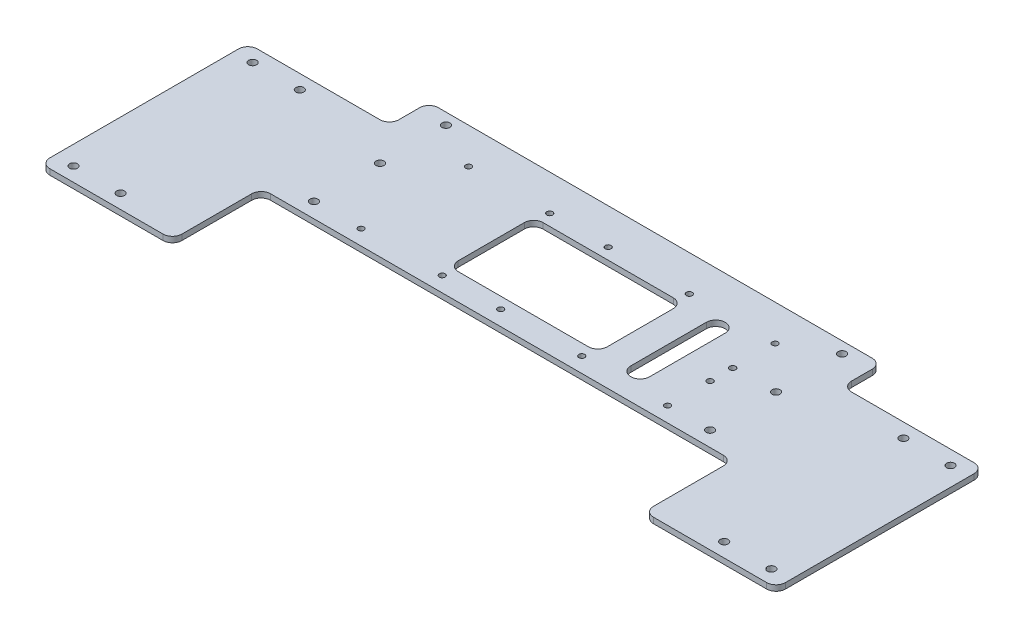
SolidWorks part; units mm, degrees
material "Thornel Mat VMA"
ref_plane "前视基准面" through (0, 0, 0) normal (0, 0, 1) x (1, 0, 0)
ref_plane "上视基准面" through (0, 0, 0) normal (0, 1, 0) x (1, 0, 0)
ref_plane "右视基准面" through (0, 0, 0) normal (1, 0, 0) x (0, 0, -1)
sketch "草图1" plane through (0, 0, 0) normal (0, 1, 0) x (1, 0, 0)
  line L0 (31.5759, -198.8718) -> (31.5759, 46.1282) construction
  line L1 (151.5759, -32.8718) -> (-88.4241, -32.8718)
  line L7 (-88.4241, -198.8718) -> (151.5759, -198.8718)
  line L8 (-88.4241, -198.8718) -> (-88.4241, -32.8718)
  line L10 (151.5759, -198.8718) -> (151.5759, -32.8718)
  line L16 (6.5759, -59.8718) -> (56.5759, -59.8718) construction
  line L18 (6.5759, -34.8718) -> (6.5759, -84.8718) construction
  line L19 (6.5759, -84.8718) -> (56.5759, -84.8718) construction
  line L20 (56.5759, -34.8718) -> (56.5759, -84.8718) construction
  line L21 (151.5759, -94.8718) -> (-88.4241, -94.8718) construction
  line L22 (-88.4241, -49.8718) -> (151.5759, -49.8718) construction
  circle A5 centre (6.5759, -84.8718) radius 1.6 construction
  circle A6 centre (56.5759, -84.8718) radius 1.6 construction
  point P6 (0, -121.2547)
  dimension "D2" = 166
  dimension "D4" = 240
  dimension "D9" = 10
  dimension "D12" = 50
  dimension "D15" = 45
extrude "构型与裁判孔" add sketch "草图1" along normal blind 3 contours L10 L21 L8 L7 region at (31.5759, 0, 115.8718)
sketch "草图4" plane through (0, 3, 0) normal (0, 1, 0) x (1, 0, 0)
  line L0 (-73.4241, -108.8718) -> (-73.4241, -198.8718) construction
  line L1 (77.0759, -32.8718) -> (77.0759, -198.8718) construction
  line L2 (151.5759, -32.8718) -> (-88.4241, -32.8718) construction
  line L3 (-88.4241, -198.8718) -> (-88.4241, -32.8718) construction
  line L4 (31.5759, -32.8718) -> (31.5759, -198.8718) construction
  line L5 (-88.4241, -198.8718) -> (151.5759, -198.8718) construction
  line L6 (-13.9241, -32.8718) -> (-13.9241, -198.8718) construction
  line L7 (-88.4241, -198.8718) -> (151.5759, -198.8718) construction
  line L8 (-88.4241, -198.8718) -> (151.5759, -198.8718) construction
  circle A0 centre (-73.4241, -73.8718) radius 2.1
  circle A1 centre (136.5759, -178.8718) radius 2.1
  circle A2 centre (-73.4241, -108.8718) radius 2.1
  circle A3 centre (-73.4241, -143.8718) radius 2.1
  circle A4 centre (-73.4241, -178.8718) radius 2.1
  circle A5 centre (136.5759, -143.8718) radius 2.1
  circle A6 centre (136.5759, -108.8718) radius 2.1
  circle A7 centre (136.5759, -73.8718) radius 2.1
  circle A8 centre (-73.4241, -38.8718) radius 2.1
  circle A9 centre (136.5759, -38.8718) radius 2.1
  circle A10 centre (77.0759, -188.8718) radius 1.55
  circle A11 centre (-13.9241, -188.8718) radius 1.55
  circle A12 centre (77.0759, -153.8718) radius 1.55
  circle A13 centre (-13.9241, -153.8718) radius 1.55
  dimension "D2" = 20
  dimension "D5" = 35
  dimension "D6" = 35
  dimension "D7" = 35
  dimension "D3" = 4.2
  dimension "D4" = 35
  dimension "D8" = 3.1
  dimension "D9" = 10
  dimension "D10" = 35
  dimension "D1" = 15
  dimension "D11" = 91
extrude "切除-拉伸3" cut sketch "草图4" against normal through all
sketch "草图5" plane through (0, 3, 0) normal (0, 1, 0) x (1, 0, 0)
  line L0 (71.0759, -57.8718) -> (-7.9241, -57.8718)
  line L1 (71.0759, -57.8718) -> (71.0759, -102.8718)
  line L2 (71.0759, -102.8718) -> (-7.9241, -102.8718)
  line L3 (-7.9241, -57.8718) -> (-7.9241, -102.8718)
  line L4 (71.0759, -57.8718) -> (-7.9241, -102.8718) construction
  line L5 (71.0759, -102.8718) -> (-7.9241, -57.8718) construction
  line L6 (31.5759, -32.8718) -> (31.5759, -104.1535) construction
  line L7 (71.0759, -80.3718) -> (-7.9241, -80.3718) construction
  line L8 (31.5759, -57.8718) -> (31.5759, -102.8718) construction
  line L9 (151.5759, -32.8718) -> (-88.4241, -32.8718) construction
  line L10 (91.0759, -100.3718) -> (91.0759, -60.3718) construction
  line L11 (86.0759, -100.3718) -> (86.0759, -60.3718)
  line L12 (96.0759, -100.3718) -> (96.0759, -60.3718)
  line L13 (31.5759, -102.8718) -> (31.5759, -198.8718) construction
  line L16 (-88.4241, -198.8718) -> (151.5759, -198.8718) construction
  line L17 (1.5759, -124.8718) -> (61.5759, -124.8718) construction
  line L18 (1.5759, -117.8718) -> (61.5759, -117.8718)
  line L19 (1.5759, -131.8718) -> (21.5759, -131.8718)
  line L20 (41.5759, -131.8718) -> (61.5759, -131.8718)
  line L21 (-73.4241, -143.8718) -> (136.5759, -143.8718) construction
  circle A0 centre (-5.4241, -51.8718) radius 1.55
  circle A1 centre (68.5759, -51.8718) radius 1.55
  circle A2 centre (68.5759, -108.8718) radius 1.55
  circle A3 centre (-5.4241, -108.8718) radius 1.55
  arc A4 (86.0759, -100.3718) -> (96.0759, -100.3718) centre (91.0759, -100.3718) ccw
  arc A5 (96.0759, -60.3718) -> (86.0759, -60.3718) centre (91.0759, -60.3718) ccw
  arc A8 (1.5759, -117.8718) -> (1.5759, -131.8718) centre (1.5759, -124.8718) ccw
  arc A9 (61.5759, -131.8718) -> (61.5759, -117.8718) centre (61.5759, -124.8718) ccw
  arc A10 (21.5759, -131.8718) -> (41.5759, -131.8718) centre (31.5759, -131.8718) ccw
  circle A11 centre (-45.4241, -143.8718) radius 10
  circle A12 centre (-73.4241, -143.8718) radius 2.1 construction
  circle A13 centre (108.5759, -143.8718) radius 10
  point P1 (110.5236, -62.9669)
  point P23 (91.0759, -80.3718)
  point P33 (31.5759, -124.8718)
  dimension "D3" = 3.1
  dimension "D7" = 5
  dimension "D10" = 7
  dimension "D13" = 20
  dimension "D14" = 28
  dimension "D1" = 79
  dimension "D2" = 45
  dimension "D4" = 37
  dimension "D5" = 28.5
  dimension "D6" = 25
  dimension "D8" = 40
  dimension "D9" = 15
  dimension "D11" = 60
  dimension "D12" = 15
extrude "切除-拉伸4" cut sketch "草图5" against normal through all
sketch "草图9" plane through (0, 0, 0) normal (0, -1, 0) x (1, 0, 0)
  line L0 (-1005.4241, 108.8718) -> (48994.5759, 108.8718) construction
  line L1 (-88.4241, 198.8718) -> (-88.4241, 32.8718) construction
  line L2 (-7.9241, 57.8718) -> (-7.9241, 102.8718) construction
  line L3 (-7.9241, 57.8718) -> (-7.9241, 102.8718) construction
  line L4 (-7.9241, 80.3718) -> (10.0801, 80.3718) construction
  line L5 (-1005.4241, 51.8718) -> (48994.5759, 51.8718) construction
  line L8 (91.0759, 105.3718) -> (91.0759, 78.9227) construction
  circle A0 centre (-5.4241, 108.8718) radius 1.55 construction
  circle A1 centre (-5.4241, 108.8718) radius 1.55 construction
  circle A2 centre (-73.4241, 108.8718) radius 2.1 construction
  circle A3 centre (-73.4241, 108.8718) radius 2.1 construction
  circle A4 centre (68.5759, 108.8718) radius 1.55 construction
  circle A5 centre (68.5759, 108.8718) radius 1.55
  circle A6 centre (-48.4241, 108.8718) radius 1.55
  circle A7 centre (25.5759, 108.8718) radius 1.55
  circle A8 centre (-5.4241, 51.8718) radius 1.55 construction
  circle A9 centre (25.5759, 51.8718) radius 1.55
  circle A10 centre (-48.4241, 51.8718) radius 1.55
  circle A12 centre (114.0759, 51.8718) radius 1.55
  circle A15 centre (68.5759, 51.8718) radius 1.55 construction
  circle A16 centre (114.0759, 74.3718) radius 1.6
  circle A17 centre (136.5759, 38.8718) radius 2.1 construction
  circle A18 centre (114.0759, 86.3718) radius 1.6
  circle A19 centre (114.0759, 108.8718) radius 1.55
  circle A20 centre (114.0759, 131.3718) radius 1.6
  arc A21 (96.0759, 100.3718) -> (86.0759, 100.3718) centre (91.0759, 100.3718) ccw construction
  circle A22 centre (68.0759, 131.3718) radius 1.6
  dimension "D3" = 3.1
  dimension "D5" = 3.1
  dimension "D7" = 3.2
  dimension "D8" = 3.1
  dimension "D9" = 45.5
  dimension "D10" = 22.5
  dimension "D1" = 15
  dimension "D2" = 74
  dimension "D4" = 25
  dimension "D6" = 74
  dimension "D11" = 22.5
sketch "草图6" plane through (0, 0, 0) normal (0, 1, 0) x (1, 0, 0)
  line L0 (-63.0381, -108.8718) -> (146.9619, -108.8718) construction
  line L1 (-88.4241, -53.8718) -> (-163.4241, -53.8718)
  line L2 (-88.4241, -198.8718) -> (-88.4241, -32.8718) construction
  line L3 (-163.4241, -53.8718) -> (-163.4241, -163.8718)
  line L4 (-73.4241, -108.8718) -> (136.5759, -108.8718) construction
  line L5 (-88.4241, -53.8718) -> (-88.4241, -163.8718)
  line L6 (-88.4241, -163.8718) -> (-163.4241, -163.8718)
  line L7 (31.5759, -32.8718) -> (31.5759, -198.8718) construction
  line L8 (151.5759, -32.8718) -> (-88.4241, -32.8718) construction
  line L9 (-88.4241, -198.8718) -> (151.5759, -198.8718) construction
  line L10 (151.5759, -53.8718) -> (151.5759, -163.8718)
  line L11 (151.5759, -163.8718) -> (226.5759, -163.8718)
  line L12 (226.5759, -53.8718) -> (226.5759, -163.8718)
  line L13 (151.5759, -53.8718) -> (226.5759, -53.8718)
  line L14 (-153.4241, -53.8718) -> (-153.4241, -163.8718) construction
  line L15 (-128.4241, -53.8718) -> (-128.4241, -163.8718) construction
  line L16 (-153.4241, -61.3718) -> (-128.4241, -61.3718) construction
  circle A0 centre (-153.4241, -61.3718) radius 2.1
  circle A1 centre (-153.4241, -156.3718) radius 2.1
  circle A2 centre (216.5759, -156.3718) radius 2.1
  circle A3 centre (216.5759, -61.3718) radius 2.1
  circle A4 centre (-128.4241, -61.3718) radius 2.1
  circle A5 centre (-128.4241, -156.3718) radius 2.1
  circle A6 centre (191.5759, -156.3718) radius 2.1
  circle A7 centre (191.5759, -61.3718) radius 2.1
  point P15 (-88.4241, -108.8718)
  point P16 (-163.4241, -108.8718)
  dimension "D4" = 95
  dimension "D6" = 4.2
  dimension "D7" = 4.2
  dimension "D1" = 75
  dimension "D2" = 55
  dimension "D3" = 10
  dimension "D5" = 25
extrude "凸台-拉伸1" add sketch "草图6" along normal blind 3
fillet "圆角1" radius 5 18 edges at (71.0759, 1.5, 102.8718) (-7.9241, 1.5, 102.8718) (-7.9241, 1.5, 57.8718) (71.0759, 1.5, 57.8718) (151.5759, 1.5, 32.8718) (-88.4241, 1.5, 32.8718) (151.5759, 1.5, 53.8718) (151.5759, 1.5, 163.8718) (-88.4241, 1.5, 163.8718) (-88.4241, 1.5, 53.8718) (226.5759, 1.5, 53.8718) (226.5759, 1.5, 163.8718) (151.5759, 1.5, 198.8718) (-88.4241, 1.5, 198.8718) (-163.4241, 1.5, 53.8718) (-163.4241, 1.5, 163.8718) (41.5759, 1.5, 131.8718) (21.5759, 1.5, 131.8718)
sketch "草图7" plane through (0, 3, 0) normal (0, 1, 0) x (1, 0, 0)
  line L0 (146.5759, -32.8718) -> (-83.4241, -32.8718) construction
  line L1 (-48.4241, -32.8718) -> (-48.4241, -82.8718)
  line L2 (-88.4241, -48.8718) -> (-88.4241, -37.8718) construction
  line L3 (-93.4241, -82.8718) -> (-48.4241, -82.8718)
  line L4 (-83.4241, -198.8718) -> (146.5759, -198.8718) construction
  line L5 (31.5759, -198.8718) -> (31.5759, 61.0332) construction
  line L6 (156.5759, -82.8718) -> (111.5759, -82.8718)
  line L7 (151.7733, -149.2908) -> (156.5759, -82.8718)
  line L8 (111.5759, -32.8718) -> (111.5759, -82.8718)
  line L10 (-48.4241, -32.8718) -> (111.5759, -32.8718)
  line L11 (-93.4241, -82.8718) -> (156.5759, -82.8718)
  line L12 (-93.4241, -82.8718) -> (-93.4241, -208.1915)
  line L13 (-93.4241, -208.1915) -> (156.5759, -208.1915)
  line L14 (156.5759, -82.8718) -> (156.5759, -208.1915)
  line L19 (-48.4241, -32.8718) -> (-48.4241, -82.8718)
  line L20 (-48.4241, -82.8718) -> (111.5759, -82.8718)
  line L21 (111.5759, -32.8718) -> (111.5759, -82.8718)
  dimension "D1" = 50
  dimension "D2" = 40
  dimension "D3" = 0
extrude "切除-拉伸5" [suppressed] cut sketch "草图7" against normal blind 10
fillet "圆角2" [suppressed] radius 10
fillet "圆角3" [suppressed] radius 10
sketch "草图8" plane through (0, 3, 0) normal (0, 1, 0) x (1, 0, 0)
  circle A0 centre (31.5759, -158.2052) radius 35.8 construction
  circle A1 centre (31.5759, -158.2052) radius 35.8 construction
  circle A2 centre (31.5759, -158.2052) radius 39
  dimension "D1" = 78
extrude "切除-拉伸6" cut sketch "草图8" against normal blind 10
extrude "切除-拉伸7" cut sketch "草图9" against normal blind 10
sketch "草图10" plane through (0, 0, 0) normal (0, -1, 0) x (1, 0, 0)
  line L0 (151.5759, 193.8718) -> (151.5759, 168.8718) construction
  line L1 (-93.4241, 198.8718) -> (156.5759, 198.8718)
  line L2 (-93.4241, 198.8718) -> (-93.4241, 116.8718)
  line L3 (-93.4241, 116.8718) -> (156.5759, 116.8718)
  line L4 (156.5759, 198.8718) -> (156.5759, 116.8718)
  line L5 (151.5759, 193.8718) -> (151.5759, 168.8718) construction
  line L6 (-163.4241, 58.8718) -> (-163.4241, 158.8718) construction
  line L7 (226.5759, 158.8718) -> (226.5759, 58.8718) construction
  line L8 (-83.4241, 198.8718) -> (146.5759, 198.8718) construction
  dimension "D1" = 82
  dimension "D2" = 70
  dimension "D3" = 70
  dimension "D4" = 0
extrude "切除-拉伸8" cut sketch "草图10" against normal blind 10
fillet "圆角4" radius 5 4 edges at (156.5759, 1.5, 116.8718) (156.5759, 1.5, 163.8718) (-93.4241, 1.5, 116.8718) (-93.4241, 1.5, 163.8718)
